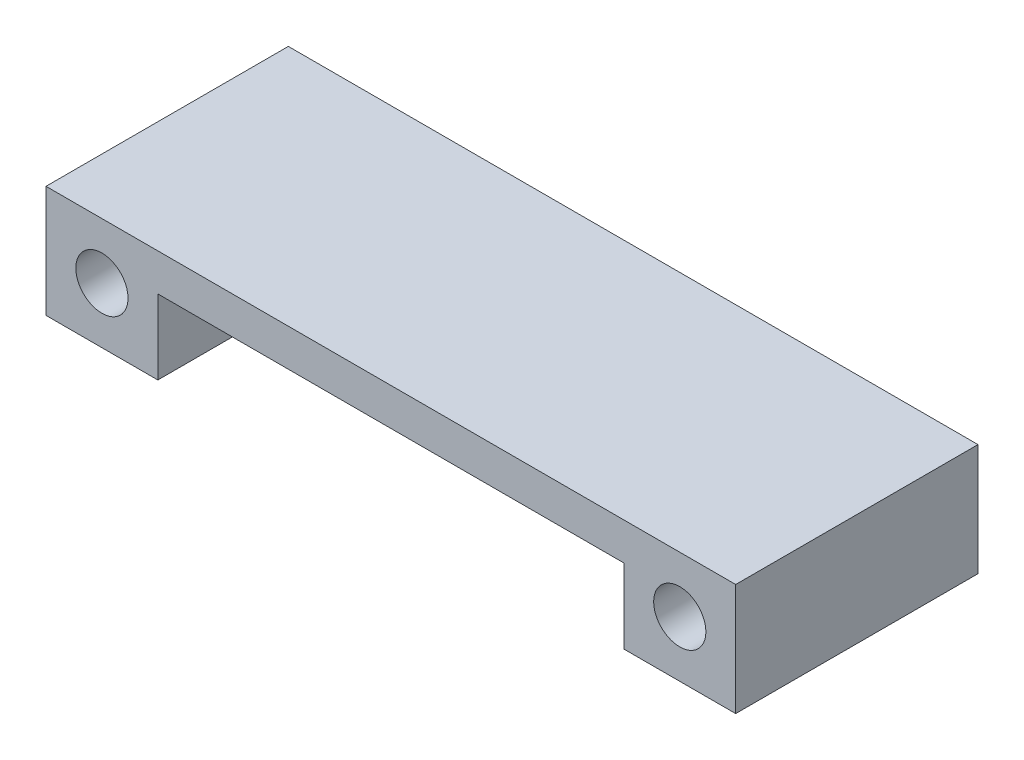
SolidWorks part; units mm, degrees
ref_plane "Front Plane" through (0, 0, 0) normal (0, 0, 1) x (1, 0, 0)
ref_plane "Top Plane" through (0, 0, 0) normal (0, 1, 0) x (1, 0, 0)
ref_plane "Right Plane" through (0, 0, 0) normal (1, 0, 0) x (0, 0, -1)
sketch "Sketch1" plane through (0, 0, 0) normal (0, 0, 1) x (1, 0, 0)
  line L0 (0, 0) -> (0, -16252.7255) construction
  line L1 (-12.5, 0) -> (12.5, 0)
  line L2 (12.5, 0) -> (12.5, -4)
  line L3 (12.5, -4) -> (18.5, -4)
  line L4 (18.5, -4) -> (18.5, 2)
  line L5 (18.5, 2) -> (-18.5, 2)
  line L6 (12.5, -4) -> (18.5, 2) construction
  line L7 (-12.5, -4) -> (-18.5, 2) construction
  line L8 (-18.5, -4) -> (-18.5, 2)
  line L9 (-12.5, -4) -> (-18.5, -4)
  line L10 (-12.5, 0) -> (-12.5, -4)
  circle A0 centre (15.5, -1) radius 1.4
  circle A1 centre (-15.5, -1) radius 1.4
  point P15 (0, 2)
  point P17 (0, 0)
  dimension "D2" = 2.8
  dimension "D1" = 37
  dimension "D3" = 3
  dimension "D4" = 3
  dimension "D5" = 2
extrude "Boss-Extrude1" add sketch "Sketch1" along normal blind 13 contours L10 L1 L2 L3 L4 L5 L8 L9 A0 A1 region at (-12.8748, -2, 0)
